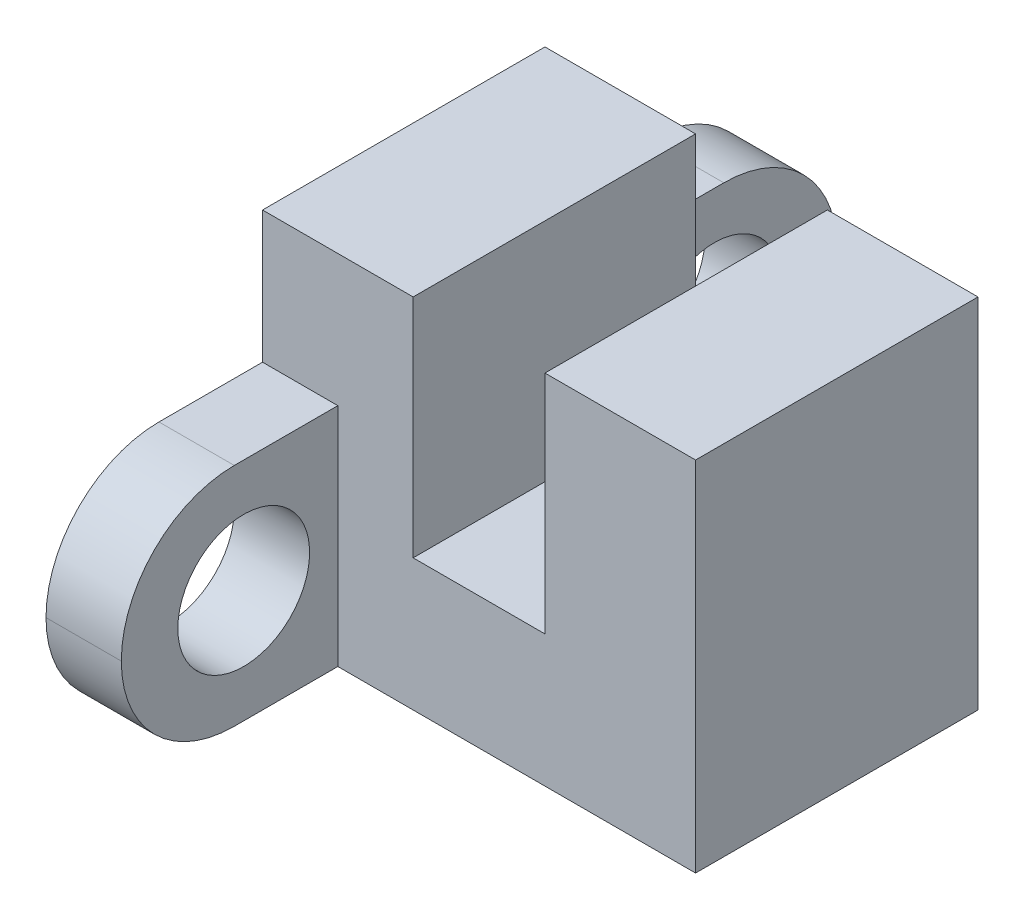
SolidWorks part; units mm, degrees
ref_plane "Front Plane" through (0, 0, 0) normal (0, 0, 1) x (1, 0, 0)
ref_plane "Top Plane" through (0, 0, 0) normal (0, 1, 0) x (1, 0, 0)
ref_plane "Right Plane" through (0, 0, 0) normal (1, 0, 0) x (0, 0, -1)
sketch "Sketch2" plane through (0, 0, 0) normal (0, 0, 1) x (1, 0, 0)
  line L1 (0, 0) -> (11.5, 0)
  line L2 (0, 0) -> (0, 9.5)
  line L3 (0, 9.5) -> (11.5, 9.5)
  line L4 (11.5, 0) -> (11.5, 9.5)
  line L5 (4, 9.5) -> (7.5, 9.5)
  line L6 (4, 9.5) -> (4, 3.5)
  line L7 (4, 3.5) -> (7.5, 3.5)
  line L8 (7.5, 9.5) -> (7.5, 3.5)
  dimension "D1" = 9.5
  dimension "D2" = 11.5
  dimension "D3" = 4
  dimension "D4" = 4
  dimension "D5" = 3.5
extrude "Boss-Extrude2" add sketch "Sketch2" along normal blind 7.5 contours L3 L8 L7 L6 L2 L1 L4 region at (0.1492, 4.75, 0)
sketch "Sketch3" plane through (0, 0, 0) normal (-1, 0, 0) x (0, 0, 1)
  line L0 (7.5, 0) -> (0, 0) construction
  line L1 (-5.75, 0) -> (13.25, 0)
  line L2 (-5.75, 0) -> (-5.75, 6)
  line L3 (-5.75, 6) -> (13.25, 6)
  line L4 (13.25, 0) -> (13.25, 6)
  line L5 (3.75, 9.5) -> (3.75, 0) construction
  line L6 (7.5, 9.5) -> (0, 9.5) construction
  circle A0 centre (-2.5, 3) radius 1.75
  circle A1 centre (10, 3) radius 1.75
  dimension "D3" = 3.5
  dimension "D5" = 3.5
  dimension "D1" = 3.25
  dimension "D2" = 19
  dimension "D4" = 6
  dimension "D6" = 3.25
  dimension "D7" = 3
extrude "Boss-Extrude3" add sketch "Sketch3" against normal blind 2
fillet "Fillet1" radius 3 4 edges at (1, 0, 13.25) (1, 6, 13.25) (1, 0, -5.75) (1, 6, -5.75)
